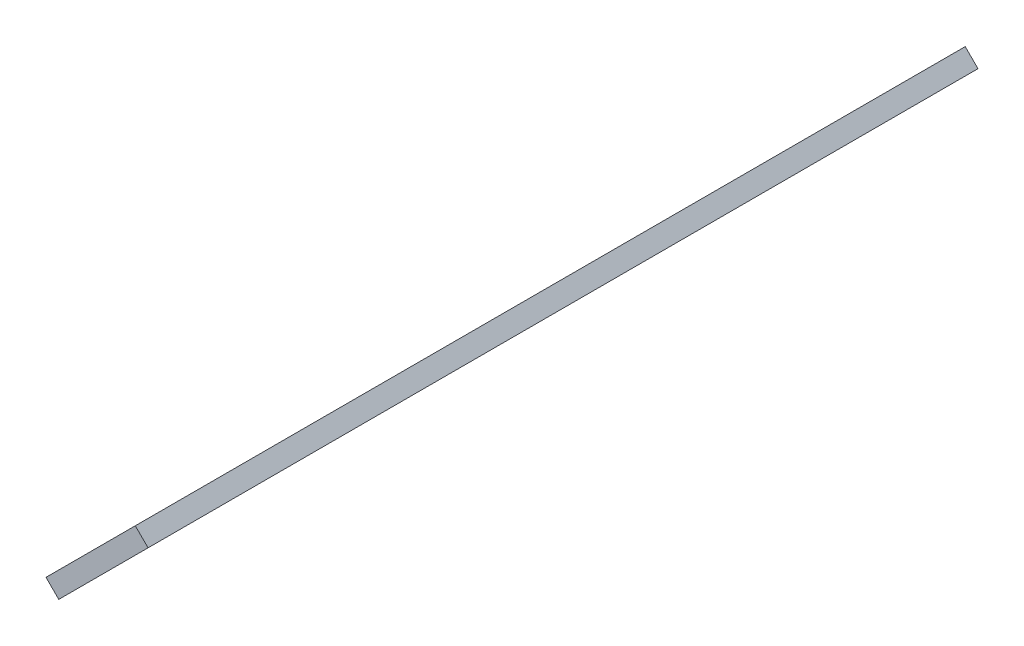
SolidWorks part; units mm, degrees
ref_plane "Front Plane" through (0, 0, 0) normal (0, 0, 1) x (1, 0, 0)
ref_plane "Top Plane" through (0, 0, 0) normal (0, 1, 0) x (1, 0, 0)
ref_plane "Right Plane" through (0, 0, 0) normal (1, 0, 0) x (0, 0, -1)
sketch "Sketch1" plane through (0, 0, 0) normal (0, 0, 1) x (1, 0, 0)
  line L0 (91.6648, 29.3027) -> (52.5461, -9.816) construction
  line L2 (78.5772, 20.7053) -> (74.1015, 16.2295) construction
  line L3 (78.5917, 11.7394) -> (83.0674, 16.2151) construction
  line L4 (39.9621, 9.9289) -> (35.472, 14.4191)
  line L5 (39.9621, 9.9289) -> (71.393, 41.3598)
  line L6 (35.472, 14.4191) -> (66.9029, 45.85)
  line L7 (71.393, 41.3598) -> (66.9029, 45.85)
  line L8 (108.2121, 4.5408) -> (76.7812, -26.8901) construction
  line L9 (76.7812, -26.8901) -> (72.2911, -22.4) construction
  line L10 (103.722, 9.0309) -> (72.2911, -22.4) construction
extrude "Boss-Extrude1" add sketch "Sketch1" along normal up to surface (292.1 mm away)
